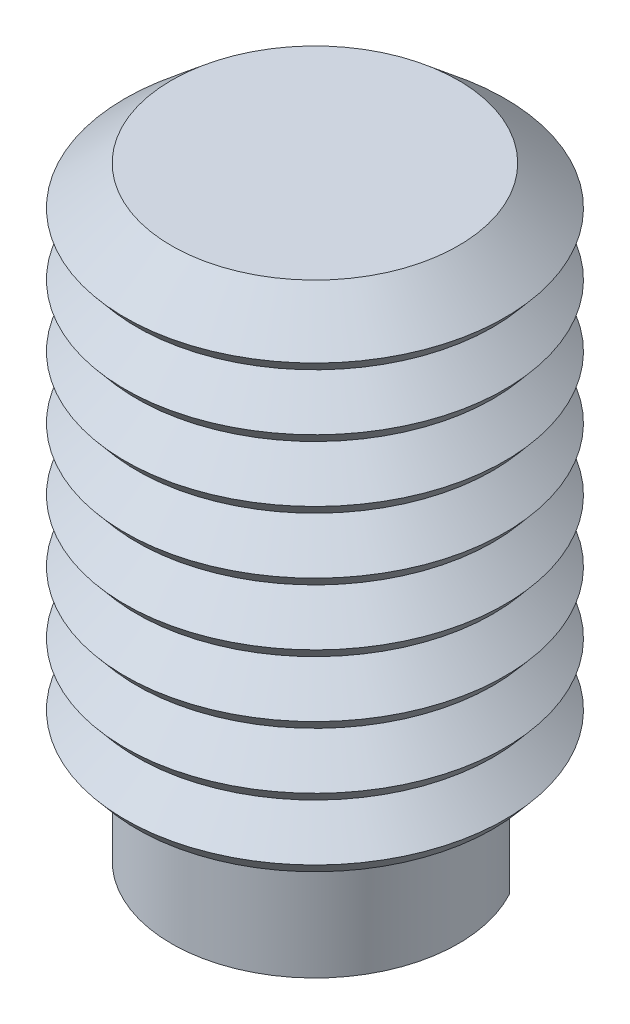
SolidWorks part; units mm, degrees
ref_plane "Front Plane" through (0, 0, 0) normal (0, 0, 1) x (1, 0, 0)
ref_plane "Top Plane" through (0, 0, 0) normal (0, 1, 0) x (1, 0, 0)
ref_plane "Right Plane" through (0, 0, 0) normal (1, 0, 0) x (0, 0, -1)
sketch "Sketch1" plane through (0, 0, 0) normal (0, 0, 1) x (1, 0, 0)
  line L0 (0, -10.8825) -> (0, -13.1825)
  line L1 (0, -13.1825) -> (-11.45, -13.1825)
  line L3 (-11.45, 33.0756) -> (0, 33.0756)
  line L4 (0, 33.0756) -> (0, 31.1175)
  line L5 (0, 31.1175) -> (-10, 31.1175)
  line L6 (-10, 31.1175) -> (-10, -10.8825)
  line L7 (-10, -10.8825) -> (0, -10.8825)
  line L8 (-11.45, 33.0756) -> (-15.16, 29.9625)
  line L9 (-11.45, 33.0756) -> (-11.45, -13.1825) construction
  line L13 (-11.45, 31.1175) -> (-10, 31.1175) construction
  line L14 (-11.45, 31.1175) -> (-11.45, 28.1175)
  line L18 (-11.45, 26.1594) -> (-11.45, 23.1594)
  line L19 (-15.16, 27.4229) -> (-15.16, -17.4925) construction
  line L20 (-11.45, 23.1594) -> (-15.16, 20.0463)
  line L21 (-15.16, 20.0463) -> (-14.1958, 18.8972)
  line L22 (-14.1958, 18.8972) -> (-11.45, 21.2013)
  line L23 (-11.45, 21.2013) -> (-11.45, 18.2013)
  line L24 (-11.45, 18.2013) -> (-15.16, 15.0882)
  line L25 (-15.16, 15.0882) -> (-14.1958, 13.9391)
  line L26 (-14.1958, 13.9391) -> (-11.45, 16.2432)
  line L27 (-11.45, 16.2432) -> (-11.45, 13.2432)
  line L28 (-11.45, 13.2432) -> (-15.16, 10.1301)
  line L29 (-15.16, 10.1301) -> (-14.1958, 8.981)
  line L30 (-14.1958, 8.981) -> (-11.45, 11.285)
  line L31 (-11.45, 11.285) -> (-11.45, 8.285)
  line L32 (-11.45, 8.285) -> (-15.16, 5.172)
  line L33 (-15.16, 5.172) -> (-14.1958, 4.0229)
  line L34 (-14.1958, 4.0229) -> (-11.45, 6.3269)
  line L35 (-11.45, 6.3269) -> (-11.45, 3.3269)
  line L36 (-11.45, 3.3269) -> (-15.16, 0.2139)
  line L37 (-15.16, 0.2139) -> (-14.1958, -0.9352)
  line L38 (-14.1958, -0.9352) -> (-11.45, 1.3688)
  line L39 (-11.45, 1.3688) -> (-11.45, -1.6312)
  line L40 (-11.45, -1.6312) -> (-15.16, -4.7442)
  line L41 (-15.16, -4.7442) -> (-14.1958, -5.8933)
  line L42 (-14.1958, -5.8933) -> (-11.45, -3.5893)
  line L47 (-11.45, -3.5893) -> (-11.45, -13.1825)
  line L48 (-15.16, 29.9625) -> (-14.1958, 28.8135)
  line L49 (-14.1958, 28.8135) -> (-11.45, 31.1175)
  line L50 (-11.45, 28.1175) -> (-15.16, 25.0044)
  line L51 (-15.16, 25.0044) -> (-14.1958, 23.8554)
  line L52 (-14.1958, 23.8554) -> (-11.45, 26.1594)
  dimension "D1" = 42
  dimension "D2" = 3
  dimension "D3" = 2.3
  dimension "D4" = 10
  dimension "D5" = 1.45
  dimension "D6" = 1.5
  dimension "D7" = 1.5
  dimension "D8" = 40
  dimension "D9" = 4.8431
  dimension "D10" = 50
  dimension "D12" = 3
  dimension "D16" = 3.71
  dimension "D17" = 40
  dimension "D18" = 1.5
  dimension "D19" = 4.8431
  dimension "D20" = 3
  dimension "D21" = 40
  dimension "D22" = 1.5
  dimension "D23" = 3
  dimension "D24" = 1.5
  dimension "D25" = 40
  dimension "D26" = 3
  dimension "D27" = 40
  dimension "D28" = 1.5
  dimension "D29" = 3
  dimension "D30" = 1.5
  dimension "D31" = 40
  dimension "D32" = 3
  dimension "D33" = 40
  dimension "D34" = 1.5
revolve "Revolve1" add sketch "Sketch1" angle 360 about L4
sketch "Sketch2" plane through (0, -13.1825, 0) normal (0, -1, 0) x (1, 0, 0)
  circle A0 centre (0, 0) radius 8.45
  circle A1 centre (0, 0) radius 11.45 construction
  dimension "D1" = 3
extrude "Cut-Extrude1" cut sketch "Sketch2" against normal blind 39
sketch "Sketch3" plane through (0, 31.1175, 0) normal (0, -1, 0) x (1, 0, 0)
  line L2 (-6.2077, 0) -> (11.0938, 0)
  line L3 (-6.2077, 0) -> (-6.2077, -2.8339)
  line L4 (-6.2077, -2.8339) -> (11.0938, -2.8339)
  line L5 (11.0938, 0) -> (11.0938, -2.8339)
  line L6 (-6.2077, 0) -> (11.0938, -2.8339) construction
  line L7 (-6.2077, -2.8339) -> (11.0938, 0) construction
  circle A0 centre (0, 0) radius 11.45 construction
  point P8 (2.443, -1.4169)
extrude "Boss-Extrude1" add sketch "Sketch3" along normal blind 0.25
sketch "Sketch4" plane through (0, 0, 0) normal (0, 0, 1) x (1, 0, 0)
  circle A2 centre (-1.0279, 9.5333) radius 1
  circle A3 centre (3.9721, 9.5333) radius 1
  circle A12 centre (-1.0279, 14.5333) radius 1
  circle A13 centre (3.9721, 14.5333) radius 1
  circle A15 centre (-1.0279, 19.5333) radius 1
  circle A16 centre (3.9721, 19.5333) radius 1
  circle A18 centre (-1.0279, 4.5333) radius 1
  circle A19 centre (3.9721, 4.5333) radius 1
  circle A21 centre (-1.0279, -0.4667) radius 1
  circle A22 centre (3.9721, -0.4667) radius 1
  circle A24 centre (-1.0279, -5.4667) radius 1
  circle A25 centre (3.9721, -5.4667) radius 1
  dimension "D3" = 2
  dimension "D5" = 2
  dimension "D6" = 4
extrude "Cut-Extrude2" cut sketch "Sketch4" against normal up to next and the other way blind 6
sketch "Sketch17" plane through (0, 30.8675, 0) normal (0, -1, 0) x (-1, 0, 0)
  line L1 (3.2986, 2.3036) -> (3.5764, 1.2702)
  line L2 (3.5764, 1.2702) -> (4.6104, 0.9941)
  line L3 (4.6104, 0.9941) -> (5.3664, 1.7514)
  line L4 (5.3664, 1.7514) -> (5.0886, 2.7848)
  line L5 (5.0886, 2.7848) -> (4.0547, 3.0609)
  line L6 (4.0547, 3.0609) -> (3.2986, 2.3036)
  circle A0 centre (4.3325, 2.0275) radius 0.9268 construction
extrude "Boss-Extrude6" add sketch "Sketch17" along normal blind 0.25
sketch "Sketch19" plane through (-3.6538, 0, -0.9823) normal (0.9657, 0, 0.2596) x (0.2596, 0, -0.9657)
  circle A0 centre (-0.868, 9.6343) radius 1
  circle A1 centre (4.132, 9.6343) radius 1
  circle A2 centre (-5.868, 9.6343) radius 1
  circle A3 centre (4.132, 14.6343) radius 1
  circle A4 centre (-0.868, 14.6343) radius 1
  circle A5 centre (-5.868, 14.6343) radius 1
  circle A6 centre (4.132, 19.6343) radius 1
  circle A8 centre (-5.868, 19.6343) radius 1
  circle A9 centre (4.132, 4.6343) radius 1
  circle A10 centre (-0.868, 4.6343) radius 1
  circle A11 centre (-5.868, 4.6343) radius 1
  circle A12 centre (4.132, -0.3657) radius 1
  circle A13 centre (-0.868, -0.3657) radius 1
  circle A14 centre (-5.868, -0.3657) radius 1
  circle A15 centre (4.132, -5.3657) radius 1
  circle A16 centre (-0.868, -5.3657) radius 1
  circle A17 centre (-5.868, -5.3657) radius 1
  circle A18 centre (-0.868, 19.6343) radius 1 [skipped]
  circle A19 centre (-0.868, 19.6343) radius 1
  dimension "D1" = 2
  dimension "D5" = 5
  dimension "D9" = 5
  dimension "D2" = 2
  dimension "D3" = 2
  dimension "D4" = 3
  dimension "D6" = 4
  dimension "D7" = 2
extrude "Cut-Extrude5" cut sketch "Sketch19" against normal up to next and the other way up to next
sketch "Sketch29" plane through (0, 30.8675, 0) normal (0, -1, 0) x (1, 0, 0)
  line L1 (3.9709, -0.592) -> (4.2343, -1.0482)
  line L2 (4.2343, -1.0482) -> (4.7611, -1.0482)
  line L3 (4.7611, -1.0482) -> (5.0246, -0.592)
  line L4 (5.0246, -0.592) -> (4.7611, -0.1357)
  line L5 (4.7611, -0.1357) -> (4.2343, -0.1357)
  line L6 (4.2343, -0.1357) -> (3.9709, -0.592)
  circle A0 centre (4.4977, -0.592) radius 0.4563 construction
extrude "Boss-Extrude14" add sketch "Sketch29" along normal blind 0.25
sketch "Sketch30" plane through (0, 0, -1.0482) normal (0, 0, -1) x (-1, 0, 0)
  circle A0 centre (1.4455, 19.5316) radius 1
  circle A1 centre (1.4455, 14.5316) radius 1
  circle A2 centre (1.4455, 9.5316) radius 1
  circle A3 centre (1.4455, 4.5316) radius 1
  circle A4 centre (1.4455, -0.4684) radius 1
  circle A5 centre (1.4455, -5.4684) radius 1
  dimension "D1" = 2
  dimension "D3" = 5
  dimension "D2" = 6
extrude "Cut-Extrude9" cut sketch "Sketch30" against normal up to next and the other way up to next
sketch "Sketch33" plane through (0, -13.1825, 0) normal (0, -1, 0) x (1, 0, 0)
  circle A0 centre (0, 0) radius 8.45
  circle A1 centre (0, 0) radius 11.45
extrude "Boss-Extrude15" add sketch "Sketch33" along normal blind 2
sketch "Sketch35" plane through (0, -15.1825, 0) normal (0, -1, 0) x (1, 0, 0)
  line L0 (3.7605, -8.2995) -> (3.4874, -7.6968)
  line L1 (7.0592, -5.7591) -> (6.5475, -5.3416)
  line L2 (10.069, -5.4513) -> (7.4309, -4.023)
  line L3 (2.6944, -11.1285) -> (1.9885, -8.2127)
  arc A0 (2.6944, -11.1285) -> (3.7605, -8.2995) centre (9.215, -11.9704) cw
  circle A1 centre (0, 0) radius 11.45 construction
  arc A2 (3.4874, -7.6968) -> (6.5475, -5.3416) centre (0, 0) ccw
  arc A3 (2.6944, -11.1285) -> (10.069, -5.4513) centre (0, 0) ccw
  arc A4 (7.0592, -5.7591) -> (10.069, -5.4513) centre (9.215, -11.9704) cw
  circle A5 centre (0, 0) radius 8.45
  circle A6 centre (0, 0) radius 11.45
  point P6 (6.8034, -5.5504)
  dimension "D3" = 6.5747
  dimension "D4" = 2.4117
  dimension "D5" = 8.45
  dimension "D6" = 15.1065
  dimension "D1" = 3.4533
  dimension "D2" = 3.45
extrude "Cut-Extrude11" cut sketch "Sketch35" against normal blind 6 contours A0 L0 A2 L1 A4 A3
sketch "Sketch37" plane through (0, -15.1825, 0) normal (0, -1, 0) x (1, 0, 0)
  line L0 (2.6944, -11.1285) -> (1.9885, -8.2127)
  line L1 (10.069, -5.4513) -> (7.4309, -4.023)
  line L2 (3.7605, -8.2995) -> (3.4874, -7.6968)
  line L4 (7.0592, -5.7591) -> (6.5475, -5.3416)
  arc A0 (2.6944, -11.1285) -> (3.7605, -8.2995) centre (9.215, -11.9704) cw
  circle A1 centre (0, 0) radius 11.45 construction
  arc A2 (10.069, -5.4513) -> (8.3856, -5.4482) centre (9.215, -11.9704) ccw construction
  arc A3 (6.5475, -5.3416) -> (7.4309, -4.023) centre (0, 0) ccw
  arc A5 (7.0592, -5.7591) -> (10.069, -5.4513) centre (9.215, -11.9704) cw
  arc A6 (1.9885, -8.2127) -> (3.4874, -7.6968) centre (0, 0) ccw
extrude "Cut-Extrude12" cut sketch "Sketch37" against normal blind 6
